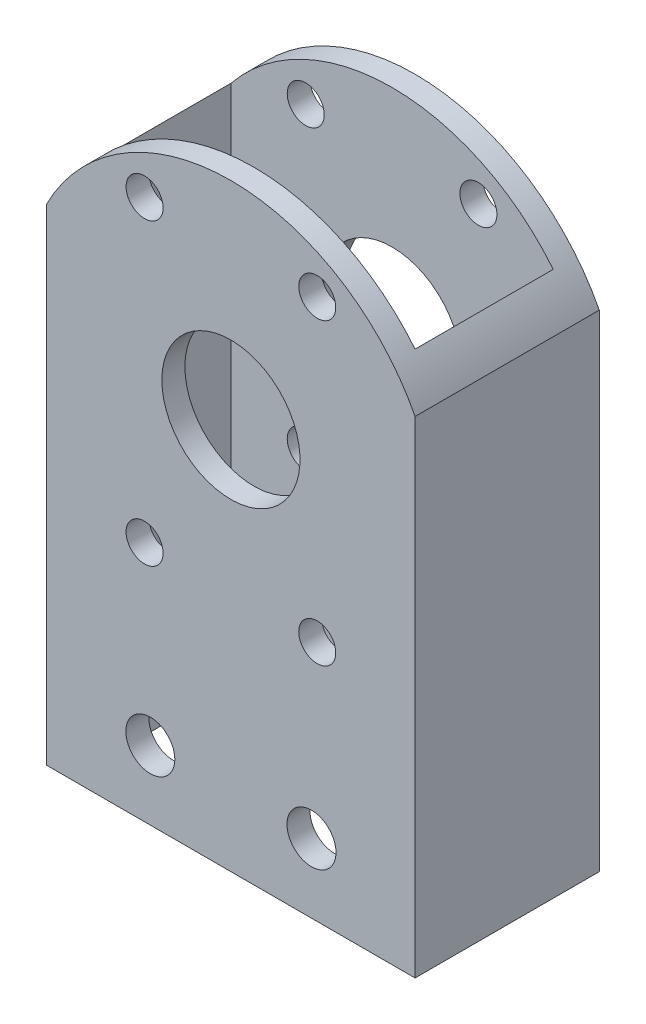
SolidWorks part; units mm, degrees
material "6061-T6 (SS)"
ref_plane "Front" through (0, 0, 0) normal (0, 0, 1) x (1, 0, 0)
ref_plane "Top" through (0, 0, 0) normal (0, 1, 0) x (1, 0, 0)
ref_plane "Right" through (0, 0, 0) normal (1, 0, 0) x (0, 0, -1)
sketch "Sketch1" plane through (0, 0, 0) normal (0, 1, 0) x (1, 0, 0)
  line L1 (-25.4, -12.7) -> (25.4, -12.7)
  line L2 (-25.4, -12.7) -> (-25.4, 12.7)
  line L3 (-25.4, 12.7) -> (25.4, 12.7)
  line L4 (25.4, -12.7) -> (25.4, 12.7)
  line L5 (-25.4, -12.7) -> (25.4, 12.7) construction
  line L6 (-25.4, 12.7) -> (25.4, -12.7) construction
  point P0 (0, 0)
  dimension "D1" = 25.4
  dimension "D2" = 50.8
extrude "Extrude-Thin1" add sketch "Sketch1" along normal blind 82.55 thin thin type one direction reverse wall 3.175
sketch "Sketch2" plane through (0, 0, -12.7) normal (0, 0, -1) x (-1, 0, 0)
  line L0 (0, 82.55) -> (0, 50.8)
  line L1 (-25.4, 82.55) -> (25.4, 82.55) construction
  line L3 (0, 41.275) -> (0, 60.325) construction
  circle A1 centre (0, 50.8) radius 23.8125
  circle A3 centre (0, 50.8) radius 9.525
  point P12 (0, 50.8)
  dimension "D1" = 19.05
  dimension "D3" = 47.625
  dimension "D2" = 31.75
hole_wizard "#10 Clearance Hole1" positions "Sketch5" profile "Sketch6" hole size "#10" standard "ANSI Inch" end condition through all
sketch "Sketch5" plane through (0, 0, -12.7) normal (0, 0, -1) x (-1, 0, 0)
  line L0 (0, 82.55) -> (0, 53.975)
  line L1 (-25.4, 82.55) -> (25.4, 82.55) construction
  line L3 (-11.9063, 74.5972) -> (11.9063, 74.5972)
  line L4 (-11.9063, 74.5972) -> (-11.9063, 33.3528)
  line L5 (-11.9063, 33.3528) -> (11.9063, 33.3528)
  line L6 (11.9063, 74.5972) -> (11.9063, 33.3528)
  circle A0 centre (0, 53.975) radius 23.8125
  point P21 (-11.9063, 74.5972)
  point P22 (11.9063, 74.5972)
  point P24 (11.9063, 33.3528)
  point P25 (-11.9063, 33.3528)
  dimension "D1" = 47.625
  dimension "D2" = 28.575
  dimension "D3" = 23.8125
sketch "Sketch6" plane through (11.9063, 33.3528, -12.7) normal (1, 0, 0) x (0, 1, 0)
  line L0 (0, 0) -> (0, 25.4)
  line L1 (0, 25.4) -> (2.5527, 25.4)
  line L2 (2.5527, 25.4) -> (2.5527, 0)
  line L5 (2.5527, 0) -> (0, 0)
  line L11 (0, -6.35) -> (0, 107.95) construction
  dimension "Thru Hole Dia." = 5.1054
  dimension "Thru Hole Depth" = 25.4
sketch "Sketch7" plane through (0, 0, -12.7) normal (0, 0, -1) x (-1, 0, 0)
  line L0 (-11.9063, 74.5972) -> (11.9063, 33.3528) construction
  circle A1 centre (0, 53.975) radius 9.525
  point P9 (0, 53.975)
  dimension "D1" = 19.05
extrude "Cut-Extrude2" cut sketch "Sketch7" against normal through all both
hole_wizard "1/4 Clearance Hole2" positions "Sketch8" profile "Sketch9" hole size "1/4" standard "ANSI Inch" end condition through all
sketch "Sketch8" plane through (0, 0, 12.7) normal (0, 0, 1) x (1, 0, 0)
  line L2 (-25.4, 82.55) -> (-25.4, 0) construction
  line L4 (-25.4, 0) -> (25.4, 0) construction
  point P0 (-11.1125, 9.525)
  point P2 (11.1125, 9.525)
  point P14 (-109.1715, 68.7854)
  dimension "D1" = 22.225
  dimension "D2" = 14.2875
  dimension "D3" = 9.525
sketch "Sketch9" plane through (-11.1125, 9.525, 12.7) normal (1, 0, 0) x (0, -1, 0)
  line L0 (0, 0) -> (0, 25.4)
  line L1 (0, 25.4) -> (3.3782, 25.4)
  line L2 (3.3782, 25.4) -> (3.3782, 0)
  line L5 (3.3782, 0) -> (0, 0)
  line L11 (0, -6.35) -> (0, 107.95) construction
  dimension "Thru Hole Dia." = 6.7564
  dimension "Thru Hole Depth" = 25.4
sketch "Sketch10" plane through (0, 0, -12.7) normal (0, 0, -1) x (-1, 0, 0)
  line L0 (-25.4, 67.0659) -> (-25.4, 82.55)
  line L1 (-25.4, 82.55) -> (25.4, 82.55)
  line L2 (25.4, 82.55) -> (25.4, 67.0659)
  line L3 (25.4, 82.55) -> (25.4, 0) construction
  arc A0 (25.4, 67.0659) -> (-25.4, 67.0659) centre (0, 53.975) ccw
  line M13 (25.4, 0) -> (25.4, 82.55)
  line M14 (25.4, 82.55) -> (-25.4, 82.55)
  line M15 (-25.4, 82.55) -> (-25.4, 0)
extrude "Cut-Extrude3" cut sketch "Sketch10" against normal through all contours A0 L1 M15 | A0 M13 M14 region at (-19.4433, 78.2444, -12.7) region at (19.4433, 78.2444, -12.7)
